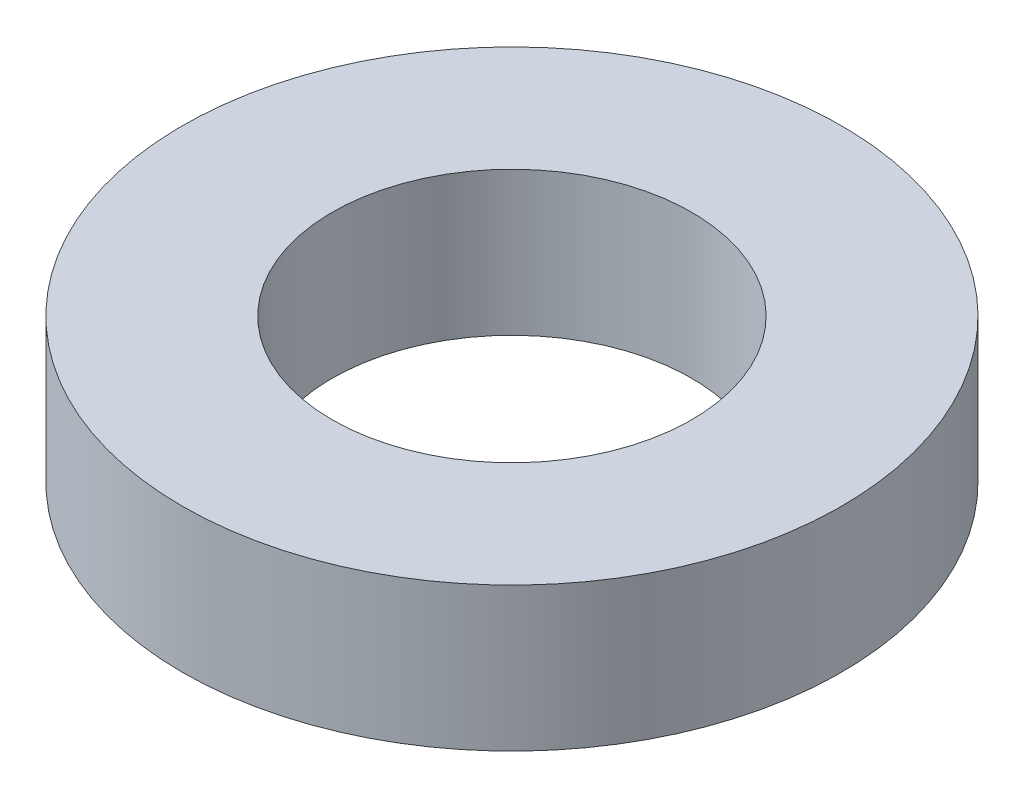
SolidWorks part; units mm, degrees
ref_plane "Front Plane" through (0, 0, 0) normal (0, 0, 1) x (1, 0, 0)
ref_plane "Top Plane" through (0, 0, 0) normal (0, 1, 0) x (1, 0, 0)
ref_plane "Right Plane" through (0, 0, 0) normal (1, 0, 0) x (0, 0, -1)
sketch "Sketch1" plane through (0, 0, 0) normal (0, 1, 0) x (1, 0, 0)
  circle A0 centre (0, 0) radius 55
  dimension "FLANGE_OD" = 110
extrude "Boss-Extrude1" add sketch "Sketch1" along normal blind 24
sketch "Sketch2" plane through (0, 0, 0) normal (0, 1, 0) x (1, 0, 0)
  circle A0 centre (0, 0) radius 30
  dimension "BORE_D" = 60
extrude "Cut-Extrude1" cut sketch "Sketch2" along normal through all
sketch "Sketch3" plane through (0, 24, 0) normal (0, 1, 0) x (1, 0, 0)
  circle A0 centre (0, 0) radius 24.5129 construction
  circle A1 centre (-24.5129, 0) radius 2.2761
  dimension "BOLT_D" = 4.5522
  dimension "BOLT_PCD" = 49.0258
extrude "Cut-Extrude2" cut sketch "Sketch3" against normal blind 16.6754 rebuild error yes
pattern_circular "CirPattern1" count 8 over 360 rebuild error yes
